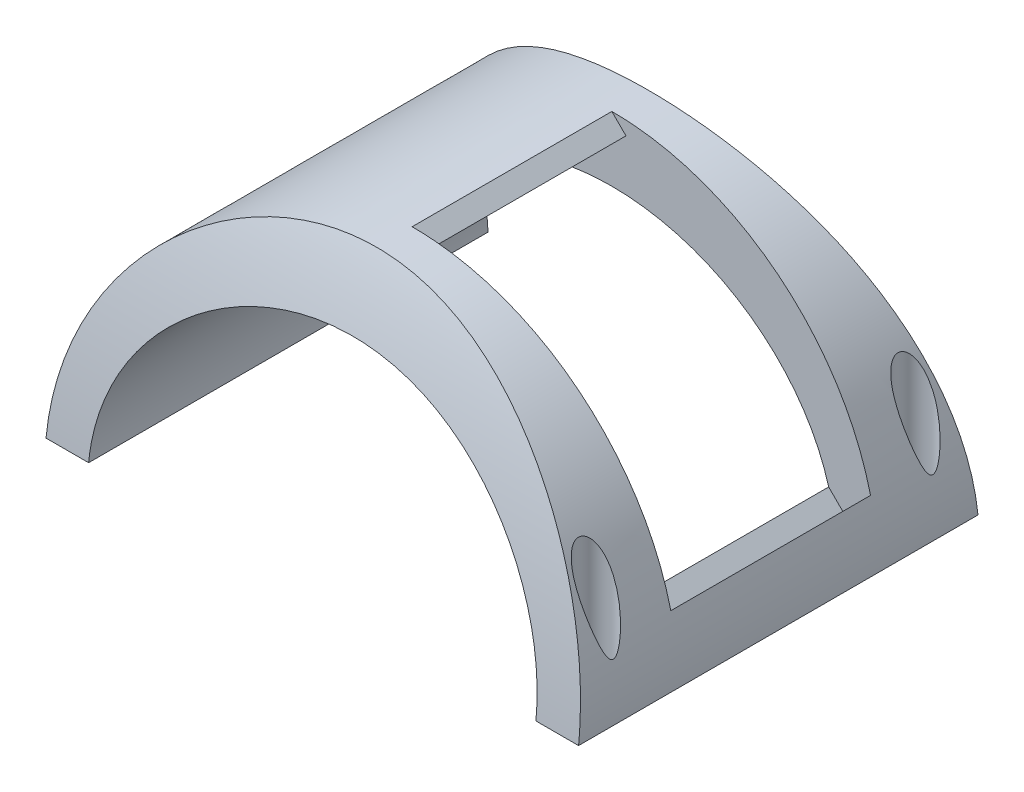
SolidWorks part; units mm, degrees
ref_plane "Front Plane" through (0, 0, 0) normal (0, 0, 1) x (1, 0, 0)
ref_plane "Top Plane" through (0, 0, 0) normal (0, 1, 0) x (1, 0, 0)
ref_plane "Right Plane" through (0, 0, 0) normal (1, 0, 0) x (0, 0, -1)
sketch "Sketch1" plane through (0, 0, 0) normal (0, 1, 0) x (1, 0, 0)
  line L1 (0, 0) -> (101.6, 0)
  line L2 (0, 0) -> (0, 76.2)
  line L3 (0, 76.2) -> (101.6, 76.2)
  line L4 (101.6, 0) -> (101.6, 76.2)
  dimension "D1" = 101.6
  dimension "D2" = 76.2
extrude "Boss-Extrude1" add sketch "Sketch1" along normal blind 2.54
sketch "Sketch2" plane through (0, 2.54, 0) normal (0, 1, 0) x (1, 0, 0)
  line L1 (0, 76.2) -> (101.6, 76.2)
  line L2 (0, 76.2) -> (0, 0)
  line L3 (0, 0) -> (101.6, 0)
  line L4 (101.6, 76.2) -> (101.6, 0)
extrude "Boss-Extrude2" add sketch "Sketch2" along normal blind 24.638
fillet "Fillet1" [suppressed] radius 2.54
sketch "Sketch3" plane through (0, 27.178, 0) normal (0, 1, 0) x (1, 0, 0)
  line L1 (0, 76.2) -> (101.6, 76.2)
  line L2 (0, 76.2) -> (0, 0)
  line L3 (0, 0) -> (101.6, 0)
  line L4 (101.6, 76.2) -> (101.6, 0)
extrude "Boss-Extrude3" add sketch "Sketch3" along normal blind 50.8 separate body
fillet "Fillet2" [suppressed] radius 2.54
sketch "Sketch4" [suppressed] plane through (0, 0, 0) normal (0, 0, 1) x (1, 0, 0)
  line L5 (0, 27.178) -> (101.6, 27.178) construction
  line L6 (2.54, 77.978) -> (99.06, 77.978) construction
  line L8 (0, 77.978) -> (101.6, 77.978)
  line L9 (0, 77.978) -> (0, 27.178)
  line L10 (0, 27.178) -> (101.6, 27.178)
  line L11 (101.6, 77.978) -> (101.6, 27.178)
  ellipse E0 centre (50.8, 27.178) end of major axis (0, 27.178) minor radius 50.8
sketch "Sketch5" plane through (0, 0, 0) normal (0, 0, 1) x (1, 0, 0)
  line L0 (0, 27.178) -> (101.6, 27.178) construction
  line L1 (0, 77.978) -> (101.6, 77.978) construction
  line L3 (0, 77.978) -> (101.6, 77.978)
  line L4 (0, 77.978) -> (0, 27.178)
  line L5 (0, 27.178) -> (101.6, 27.178)
  line L6 (101.6, 77.978) -> (101.6, 27.178)
  ellipse E0 centre (50.8, 27.178) end of major axis (0, 27.178) minor radius 50.8
  line M2 (101.6, 27.178) -> (101.6, 77.978)
  line M3 (101.6, 77.978) -> (0, 77.978)
  line M4 (0, 77.978) -> (0, 27.178)
extrude "Cut-Extrude8" cut sketch "Sketch5" against normal through all contours E0 L3 M4 region at (11.3471, 66.6309, 0)
extrude "Cut-Extrude9" cut sketch "Sketch5<3>" against normal through all contours E0 M2 M3 region at (90.2529, 66.6309, 0)
sketch "Sketch5<3>" plane through (0, 0, 0) normal (0, 0, 1) x (1, 0, 0) same geometry as "Sketch5"
sketch "Sketch6" plane through (101.6, 0, 0) normal (1, 0, 0) x (0, 0, -1)
  line L2 (76.2, 27.178) -> (0, 27.178)
  line L3 (76.2, 27.178) -> (76.2, 77.978)
  line L4 (76.2, 77.978) -> (0, 77.978)
  line L5 (0, 27.178) -> (0, 77.978)
  ellipse E0 centre (38.0388, 0) end of major axis (37.7662, -103.378) minor radius 39.489
  line M8 (76.2, 27.178) -> (0, 27.178)
  dimension "D1" = 27.178
  dimension "D2" = 76.2
extrude "Cut-Extrude10" cut sketch "Sketch6" against normal through all contours E0 L4 L5 M8 | E0 L3 L4 M8 region at (101.6, 63.1972, -72.5898) region at (101.6, 63.1459, -3.6844)
sketch "Sketch7" plane through (0, 0, 0) normal (0, 0, 1) x (1, 0, 0)
  line L0 (0, 27.178) -> (101.6, 27.178) construction
  line L1 (0, 27.178) -> (101.6, 27.178) construction
  line L2 (8.1326, 27.178) -> (93.4674, 27.178)
  ellipse E0 centre (50.8, 27.178) end of major axis (93.4674, 27.178) minor radius 38.4436
  line M4 (101.6, 27.178) -> (0, 27.178)
extrude "Cut-Extrude11" cut sketch "Sketch7" against normal through all contours E0 M4 region at (50.8, 43.494, 0)
ref_plane "Plane1" through (37.211, -37.211, 0) normal (0.7071, -0.7071, 0) x (-0.7071, -0.7071, 0)
sketch "Sketch8" plane through (37.211, -37.211, 0) normal (0.7071, -0.7071, 0) x (-0.7071, -0.7071, 0)
  line L5 (-112.4745, 19.05) -> (-91.0598, 19.05)
  line L6 (-112.4745, 19.05) -> (-112.4745, 57.15)
  line L7 (-112.4745, 57.15) -> (-91.0598, 57.15)
  line L8 (-91.0598, 19.05) -> (-91.0598, 57.15)
  line L9 (-91.0598, 76.2) -> (-71.842, 76.2) construction
  line L10 (-91.0598, 0) -> (-91.0598, 76.2) construction
  dimension "D1" = 38.1
  dimension "D2" = 19.05
  dimension "D3" = 0
extrude "Cut-Extrude12" cut sketch "Sketch8" against normal through all
sketch "Sketch9" plane through (0, 0, -57.15) normal (0, 0, 1) x (1, 0, 0)
  line L1 (94.8555, 33.9225) -> (100.1523, 39.2193)
  line L2 (50.8, 77.978) -> (65.515, 63.263)
  line L3 (92.1614, 36.6166) -> (101.6, 27.178)
  line L4 (50.8, 77.978) -> (65.515, 63.263)
  line L5 (92.1614, 36.6166) -> (101.6, 27.178)
  line L6 (92.1614, 36.6166) -> (98.9414, 43.3966)
  line L7 (92.1614, 36.6166) -> (101.6, 27.178)
  arc A1 (101.6, 27.178) -> (50.8, 77.978) centre (50.8, 27.178) ccw
  arc A3 (101.6, 27.178) -> (50.8, 77.978) centre (50.8, 27.178) ccw
  ellipse E1 centre (50.8, 27.178) end of major axis (93.4674, 27.178) minor radius 38.4436 (92.1614, 36.6166) -> (65.515, 63.263) ccw
  ellipse E2 centre (50.8, 27.178) end of major axis (93.4674, 27.178) minor radius 38.4436 (92.1614, 36.6166) -> (65.515, 63.263) ccw
  ellipse M5 centre (50.8, 27.178) end of major axis (0, 27.178) minor radius 50.8 (101.6, 27.178) -> (50.8, 77.978) ccw
  line M8 (92.1614, 36.6166) -> (101.6, 27.178)
  dimension "D2" = 58.4939
  dimension "D3" = 3.81
  dimension "D1" = 0
extrude "Boss-Extrude4" add sketch "Sketch9" along normal blind 41.402 contours M8 M5 region at (99.0328, 33.4229, -57.15)
sketch "Sketch10" plane through (64.389, 64.389, 0) normal (0.7071, 0.7071, 0) x (0, 0, -1)
  line L0 (19.05, 17.8738) -> (57.15, 17.8738)
  line L1 (19.05, -43.0862) -> (19.05, 19.2177) construction
  line L2 (57.15, 19.2177) -> (57.15, -43.0862) construction
  line L3 (19.05, -43.0862) -> (57.15, -43.0862) construction
  line L5 (57.15, 17.8738) -> (19.05, 17.8738)
  line L6 (57.15, 17.8738) -> (57.15, -1.5925)
  line L7 (57.15, -1.5925) -> (19.05, -1.5925)
  line L8 (19.05, 17.8738) -> (19.05, -1.5925)
  line M3 (19.05, 19.2177) -> (19.05, -1.5925)
  line M4 (19.05, -1.5925) -> (57.15, -1.5925)
  line M5 (57.15, -1.5925) -> (57.15, 19.2177)
  dimension "D1" = 60.96
extrude "Cut-Extrude13" cut sketch "Sketch10" against normal blind 19.558 contours L0 M3 M4 M5 region at (58.6327, 70.1453, -38.1)
sketch "Sketch12" plane through (0, 0, -57.15) normal (0, 0, 1) x (1, 0, 0)
  line L0 (51.7503, 77.0277) -> (53.4941, 75.2839)
  line L1 (53.4941, 75.2839) -> (45.6067, 67.3965)
  line L2 (50.8, 77.978) -> (51.7503, 77.0277) construction
  line L3 (53.4941, 75.2839) -> (43.2202, 65.0101)
  line L4 (92.1614, 36.6166) -> (94.8555, 33.9225)
  line L5 (94.8555, 33.9225) -> (100.1523, 39.2193)
  line L6 (50.8, 77.978) -> (51.7503, 77.0277)
  line L7 (51.7503, 77.0277) -> (38.7897, 64.0671)
  line L8 (92.1614, 36.6166) -> (94.8555, 33.9225)
  line L9 (94.8555, 33.9225) -> (100.1523, 39.2193)
  line L10 (50.8, 77.978) -> (51.7503, 77.0277)
  line L11 (51.7503, 77.0277) -> (38.7897, 64.0671)
  arc A1 (100.1523, 39.2193) -> (50.8, 77.978) centre (50.8, 27.178) ccw
  arc A2 (100.1523, 39.2193) -> (50.8, 77.978) centre (50.8, 27.178) ccw
  ellipse E1 centre (50.8, 27.178) end of major axis (93.4674, 27.178) minor radius 38.4436 (92.1614, 36.6166) -> (38.7897, 64.0671) ccw
  ellipse E2 centre (50.8, 27.178) end of major axis (93.4674, 27.178) minor radius 38.4436 (92.1614, 36.6166) -> (38.7897, 64.0671) ccw
  line M13 (51.7503, 77.0277) -> (38.7897, 64.0671)
  ellipse M14 centre (50.8, 27.178) end of major axis (93.4674, 27.178) minor radius 38.4436 (38.7897, 64.0671) -> (92.1614, 36.6166) cw
  dimension "D2" = 3.81
  dimension "D3" = 180
  dimension "D1" = 0
extrude "Boss-Extrude5" add sketch "Sketch12" along normal blind 44.958 contours L3 L1 L0 M13 M14 region at (46.7778, 70.3788, -57.15)
sketch "Sketch13" plane through (0, 0, 0) normal (0, 0, 1) x (1, 0, 0)
  line L1 (0, 27.178) -> (101.6, 27.178)
  line L2 (0, 27.178) -> (0, 0)
  line L3 (0, 0) -> (101.6, 0)
  line L4 (101.6, 27.178) -> (101.6, 0)
extrude "Cut-Extrude14" cut sketch "Sketch13" against normal through all
sketch "Sketch14" plane through (0, 0, 0) normal (0, 1, 0) x (1, 0, 0)
  line L0 (8.1326, 76.2) -> (0, 76.2) construction
  line L1 (0, 76.2) -> (0, 0) construction
  circle A0 centre (4.318, 68.58) radius 1.7526
  dimension "D1" = 3.5052
  dimension "D3" = 4.318
  dimension ".2" = 7.62
extrude "Cut-Extrude15" cut sketch "Sketch14" along normal through all
sketch "Sketch15" plane through (0, 0, 0) normal (0, 1, 0) x (1, 0, 0)
  line L0 (101.6, 38.1) -> (0, 38.1)
  line L1 (50.8, 38.1) -> (50.8, 64.1403)
  line L2 (101.6, 0) -> (101.6, 76.2)
  line L3 (0, 76.2) -> (0, 0)
  line L4 (101.6, 0) -> (101.6, 76.2)
  line L5 (0, 76.2) -> (0, 0)
  line L6 (50.8, 38.1) -> (50.8, 12.2886)
  line L7 (50.8, 12.2886) -> (50.8, 64.1403)
  spline S2 degree 3 poles (2981.9676, 327.5085) (502.6924, 70.8309) (-26.1801, -19.0961) (1.2972, 1.5028) (1.698, 1.7598) (2.6593, 2.3047) (3.222, 2.5936) (4.4911, 3.1923) (5.1991, 3.5032) (6.3711, 3.9851) (6.7799, 4.1483) (7.6299, 4.4777) (8.5134, 4.8108) (9.4634, 5.1501) (10.4467, 5.492) (10.9558, 5.6646) (12.5268, 6.1832) (13.633, 6.5306) (15.9636, 7.2235) (17.1905, 7.5697) (19.7405, 8.2474) (21.0657, 8.5796) (23.1307, 9.0625) (23.832, 9.2209) (25.2531, 9.5298) (26.6946, 9.8312) (28.1772, 10.1158) (29.6808, 10.3909) (30.4441, 10.5238) (32.7571, 10.905) (34.3287, 11.1355) (37.5328, 11.5412) (39.1684, 11.7164) (42.4655, 11.9995) (44.1308, 12.1081) (47.496, 12.2535) (49.1818, 12.2896) (52.5563, 12.2876) (54.2522, 12.2489) (57.5935, 12.1007) (60.8939, 11.8821) (64.1154, 11.5355) (66.5024, 11.2326) (67.2932, 11.1244) (68.8649, 10.8946) (69.6459, 10.7728) (71.955, 10.3918) (73.456, 10.1157) (75.6516, 9.6753) (76.375, 9.5238) (77.7928, 9.2153) (78.4885, 9.0581) (81.9021, 8.2594) (84.4285, 7.5816) (87.9171, 6.5459) (89.0311, 6.1966) (91.1243, 5.5066) (92.1078, 5.1646) (93.488, 4.6593) (93.9321, 4.4922) (94.7837, 4.1627) (95.6001, 3.8374) (96.3459, 3.5215) (97.0564, 3.2105) (97.3943, 3.0572) (98.3511, 2.607) (98.9124, 2.3197) (99.8816, 1.7723) (100.2903, 1.5115) (131.2802, -21.6498) (-548.3732, 100.1434) (-2887.1017, 257.1233) knots -2.573079 -2.573079 -2.573079 -2.573079 0.0625 0.0625 0.09375 0.09375 0.125 0.125 0.15625 0.15625 0.171875 0.171875 0.1875 0.203125 0.203125 0.21875 0.21875 0.25 0.25 0.28125 0.28125 0.3125 0.3125 0.328125 0.328125 0.34375 0.359375 0.359375 0.375 0.375 0.40625 0.40625 0.4375 0.4375 0.46875 0.46875 0.5 0.5 0.53125 0.53125 0.5625 0.59375 0.59375 0.609375 0.609375 0.625 0.625 0.65625 0.65625 0.671875 0.671875 0.6875 0.6875 0.75 0.75 0.78125 0.78125 0.8125 0.8125 0.828125 0.828125 0.84375 0.859375 0.859375 0.875 0.875 0.90625 0.90625 0.9375 0.9375 3.874255 3.874255 3.874255 3.874255 only from (0, 0) to (101.6, 0)
  spline S3 degree 3 poles (0, 0) (0, 0.358) (0.3313, 0.7787) (1.2972, 1.5028) (1.698, 1.7598) (2.6593, 2.3047) (3.222, 2.5936) (4.4911, 3.1923) (5.1991, 3.5032) (6.3711, 3.9851) (6.7799, 4.1483) (7.6299, 4.4777) (8.5134, 4.8108) (9.4634, 5.1501) (10.4467, 5.492) (10.9558, 5.6646) (12.5268, 6.1832) (13.633, 6.5306) (15.9636, 7.2235) (17.1905, 7.5697) (19.7405, 8.2474) (21.0657, 8.5796) (23.1307, 9.0625) (23.832, 9.2209) (25.2531, 9.5298) (26.6946, 9.8312) (28.1772, 10.1158) (29.6808, 10.3909) (30.4441, 10.5238) (32.7571, 10.905) (34.3287, 11.1355) (37.5328, 11.5412) (39.1684, 11.7164) (42.4655, 11.9995) (44.1308, 12.1081) (47.496, 12.2535) (49.1818, 12.2896) (52.5563, 12.2876) (54.2522, 12.2489) (57.5935, 12.1007) (60.8939, 11.8821) (64.1154, 11.5355) (66.5024, 11.2326) (67.2932, 11.1244) (68.8649, 10.8946) (69.6459, 10.7728) (71.955, 10.3918) (73.456, 10.1157) (75.6516, 9.6753) (76.375, 9.5238) (77.7928, 9.2153) (78.4885, 9.0581) (81.9021, 8.2594) (84.4285, 7.5816) (87.9171, 6.5459) (89.0311, 6.1966) (91.1243, 5.5066) (92.1078, 5.1646) (93.488, 4.6593) (93.9321, 4.4922) (94.7837, 4.1627) (95.6001, 3.8374) (96.3459, 3.5215) (97.0564, 3.2105) (97.3943, 3.0572) (98.3511, 2.607) (98.9124, 2.3197) (99.8816, 1.7723) (100.2903, 1.5115) (101.2691, 0.7799) (101.6, 0.3577) (101.6, 0) knots 0 0 0 0 0.0625 0.0625 0.09375 0.09375 0.125 0.125 0.15625 0.15625 0.171875 0.171875 0.1875 0.203125 0.203125 0.21875 0.21875 0.25 0.25 0.28125 0.28125 0.3125 0.3125 0.328125 0.328125 0.34375 0.359375 0.359375 0.375 0.375 0.40625 0.40625 0.4375 0.4375 0.46875 0.46875 0.5 0.5 0.53125 0.53125 0.5625 0.59375 0.59375 0.609375 0.609375 0.625 0.625 0.65625 0.65625 0.671875 0.671875 0.6875 0.6875 0.75 0.75 0.78125 0.78125 0.8125 0.8125 0.828125 0.828125 0.84375 0.859375 0.859375 0.875 0.875 0.90625 0.90625 0.9375 0.9375 1 1 1 1
  spline S4 degree 3 poles (-2892.9971, -93.0241) (-534.9455, -23.9944) (116.2472, 94.0863) (101.269, 75.5342) (101.166, 75.4278) (100.9188, 75.2064) (100.7745, 75.0914) (100.2826, 74.7356) (99.8754, 74.4835) (99.1468, 74.0832) (98.8839, 73.9459) (98.3205, 73.6651) (98.0202, 73.5216) (97.0641, 73.0825) (96.3534, 72.778) (94.7846, 72.1478) (93.9317, 71.824) (92.5532, 71.329) (92.0771, 71.1623) (91.0912, 70.8262) (90.5812, 70.6566) (89.0081, 70.1471) (87.9003, 69.8054) (85.5662, 69.1234) (84.3382, 68.7827) (81.7869, 68.1156) (80.4607, 67.7883) (77.7048, 67.1538) (76.2825, 66.8483) (74.0893, 66.4153) (73.3479, 66.2751) (71.8439, 66.0041) (71.0804, 65.8731) (68.7695, 65.498) (67.1988, 65.2711) (63.9959, 64.8719) (62.362, 64.6997) (59.0686, 64.4217) (57.4023, 64.3151) (54.0438, 64.1734) (52.3698, 64.1388) (47.363, 64.1431) (44.0454, 64.2902) (39.9239, 64.6428) (39.1034, 64.7215) (37.4782, 64.8937) (36.6722, 64.9872) (34.2738, 65.2887) (32.6971, 65.5182) (29.6218, 66.0205) (28.1219, 66.2933) (25.9273, 66.7287) (25.2052, 66.8781) (23.7898, 67.1824) (23.0952, 67.3375) (19.6854, 68.1253) (17.1588, 68.7939) (14.2489, 69.6451) (13.6785, 69.8165) (12.5704, 70.158) (12.032, 70.3282) (10.4638, 70.8368) (9.4807, 71.1728) (7.6401, 71.8345) (6.7897, 72.1577) (5.619, 72.6286) (5.2463, 72.7832) (4.536, 73.0875) (4.1982, 73.2373) (3.2433, 73.6766) (2.6828, 73.9566) (1.7143, 74.4896) (1.3065, 74.7428) (-29.1003, 96.8008) (625.1099, -20.7927) (2987.1565, -197.7701) knots -2.787775 -2.787775 -2.787775 -2.787775 0.03125 0.03125 0.046875 0.046875 0.0625 0.0625 0.09375 0.09375 0.109375 0.109375 0.125 0.125 0.15625 0.15625 0.1875 0.1875 0.203125 0.203125 0.21875 0.21875 0.25 0.25 0.28125 0.28125 0.3125 0.3125 0.34375 0.34375 0.359375 0.359375 0.375 0.375 0.40625 0.40625 0.4375 0.4375 0.46875 0.46875 0.5 0.5 0.5625 0.5625 0.578125 0.578125 0.59375 0.59375 0.625 0.625 0.65625 0.65625 0.671875 0.671875 0.6875 0.6875 0.75 0.75 0.765625 0.765625 0.78125 0.78125 0.8125 0.8125 0.84375 0.84375 0.859375 0.859375 0.875 0.875 0.90625 0.90625 0.9375 0.9375 3.826991 3.826991 3.826991 3.826991 only from (101.6, 76.2) to (0, 76.2)
  spline S7 degree 3 poles (101.6, 76.2) (101.6, 76.0288) (101.5167, 75.841) (101.269, 75.5342) (101.166, 75.4278) (100.9188, 75.2064) (100.7745, 75.0914) (100.2826, 74.7356) (99.8754, 74.4835) (99.1468, 74.0832) (98.8839, 73.9459) (98.3205, 73.6651) (98.0202, 73.5216) (97.0641, 73.0825) (96.3534, 72.778) (94.7846, 72.1478) (93.9317, 71.824) (92.5532, 71.329) (92.0771, 71.1623) (91.0912, 70.8262) (90.5812, 70.6566) (89.0081, 70.1471) (87.9003, 69.8054) (85.5662, 69.1234) (84.3382, 68.7827) (81.7869, 68.1156) (80.4607, 67.7883) (77.7048, 67.1538) (76.2825, 66.8483) (74.0893, 66.4153) (73.3479, 66.2751) (71.8439, 66.0041) (71.0804, 65.8731) (68.7695, 65.498) (67.1988, 65.2711) (63.9959, 64.8719) (62.362, 64.6997) (59.0686, 64.4217) (57.4023, 64.3151) (54.0438, 64.1734) (52.3698, 64.1388) (47.363, 64.1431) (44.0454, 64.2902) (39.9239, 64.6428) (39.1034, 64.7215) (37.4782, 64.8937) (36.6722, 64.9872) (34.2738, 65.2887) (32.6971, 65.5182) (29.6218, 66.0205) (28.1219, 66.2933) (25.9273, 66.7287) (25.2052, 66.8781) (23.7898, 67.1824) (23.0952, 67.3375) (19.6854, 68.1253) (17.1588, 68.7939) (14.2489, 69.6451) (13.6785, 69.8165) (12.5704, 70.158) (12.032, 70.3282) (10.4638, 70.8368) (9.4807, 71.1728) (7.6401, 71.8345) (6.7897, 72.1577) (5.619, 72.6286) (5.2463, 72.7832) (4.536, 73.0875) (4.1982, 73.2373) (3.2433, 73.6766) (2.6828, 73.9566) (1.7143, 74.4896) (1.3065, 74.7428) (0.3305, 75.4508) (0, 75.8576) (0, 76.2) knots 0 0 0 0 0.03125 0.03125 0.046875 0.046875 0.0625 0.0625 0.09375 0.09375 0.109375 0.109375 0.125 0.125 0.15625 0.15625 0.1875 0.1875 0.203125 0.203125 0.21875 0.21875 0.25 0.25 0.28125 0.28125 0.3125 0.3125 0.34375 0.34375 0.359375 0.359375 0.375 0.375 0.40625 0.40625 0.4375 0.4375 0.46875 0.46875 0.5 0.5 0.5625 0.5625 0.578125 0.578125 0.59375 0.59375 0.625 0.625 0.65625 0.65625 0.671875 0.671875 0.6875 0.6875 0.75 0.75 0.765625 0.765625 0.78125 0.78125 0.8125 0.8125 0.84375 0.84375 0.859375 0.859375 0.875 0.875 0.90625 0.90625 0.9375 0.9375 1 1 1 1
  dimension "D1" = 0
ref_axis "Axis1" through (50.8, 0, -38.1) along (0, 0, -1)
ref_axis "Axis2" through (0, 0, -38.1) along (1, 0, 0)
ref_plane "Plane8" through (50.8, 0, 0) normal (1, 0, 0) x (0, 0, -1)
ref_plane "Plane9" through (0, 0, -38.1) normal (0, 0, 1) x (-1, 0, 0)
mirror "Mirror1" about plane through (50.8, 0, 0) normal (1, 0, 0) of "Cut-Extrude15"
mirror "Mirror2" about plane through (0, 0, -38.1) normal (0, 0, 1) of "Mirror1"
sketch "Sketch16" plane through (0, 0, 0) normal (0, 1, 0) x (1, 0, 0)
  circle A1 centre (4.318, 68.58) radius 1.7526 construction
  circle A2 centre (4.318, 68.58) radius 3.3274
  dimension "D1" = 6.6548
extrude "Cut-Extrude16" cut sketch "Sketch16" along normal through all from offset 30.48 contours A2
mirror "Mirror3" about plane through (50.8, 0, 0) normal (1, 0, 0) of "Cut-Extrude16"
mirror "Mirror4" about plane through (0, 0, -38.1) normal (0, 0, 1) of "Mirror3"
